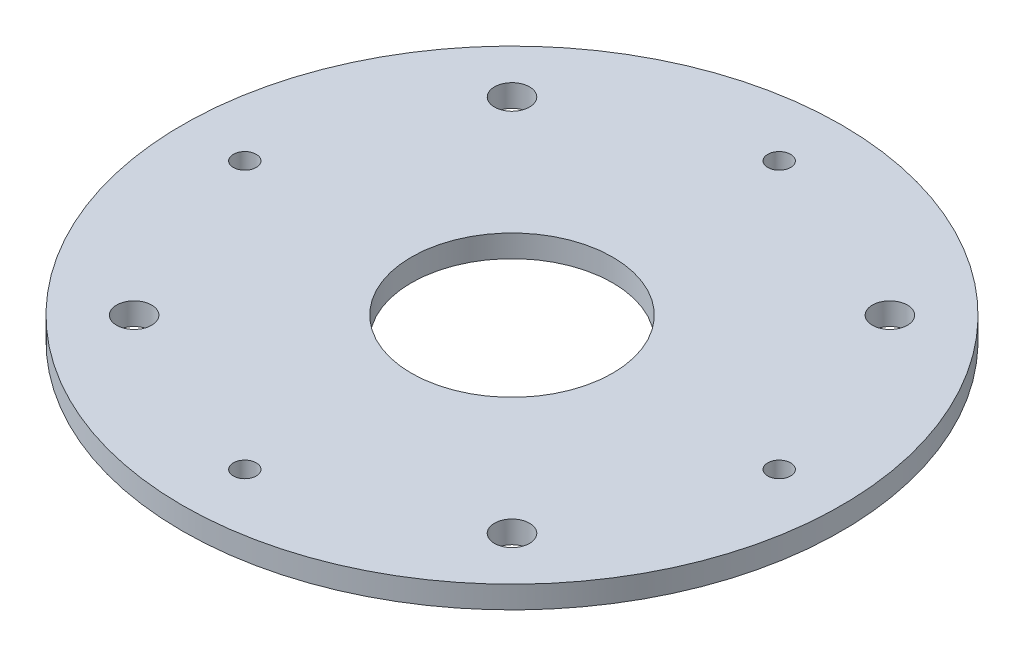
SolidWorks part; units mm, degrees
ref_plane "Front Plane" through (0, 0, 0) normal (0, 0, 1) x (1, 0, 0)
ref_plane "Top Plane" through (0, 0, 0) normal (0, 1, 0) x (1, 0, 0)
ref_plane "Right Plane" through (0, 0, 0) normal (1, 0, 0) x (0, 0, -1)
sketch "Sketch1" plane through (0, 0, 0) normal (0, 1, 0) x (1, 0, 0)
  circle A0 centre (0, 0) radius 46.99
  dimension "D1" = 93.98
extrude "Boss-Extrude1" add sketch "Sketch1" along normal blind 3.175
sketch "Sketch2" plane through (0, 3.175, 0) normal (0, 1, 0) x (1, 0, 0)
  circle A0 centre (0, 0) radius 14.351
  dimension "D1" = 28.702
extrude "Cut-Extrude1" cut sketch "Sketch2" against normal blind 3.175
hole_wizard "#4 Clearance Hole1" positions "Sketch4" profile "Sketch3" hole size "#4" standard "ANSI Inch"
sketch "Sketch4" plane through (0, 3.175, 0) normal (0, 1, 0) x (1, 0, 0)
  point P0 (0, 38.1)
  dimension "D1" = 38.1
sketch "Sketch3" plane through (0, 3.175, -38.1) normal (1, 0, 0) x (0, 0, 1)
  line L0 (0, 0) -> (0, 11.1406)
  line L1 (0, 11.1406) -> (1.6319, 10.16)
  line L2 (1.6319, 10.16) -> (1.6319, 0)
  line L5 (1.6319, 0) -> (0, 0)
  line L10 (0, 11.1406) -> (-1.632, 10.16) construction
  line L11 (0, -6.35) -> (0, 107.95) construction
  dimension "Hole Dia." = 3.2639
  dimension "Hole Depth" = 10.16
  dimension "Drill Angle" = 118
pattern_circular "CirPattern1" count 4 every 90 about axis through (0, 3.175, 0) along (0, 1, 0) of "#4 Clearance Hole1"
sketch "Sketch5" plane through (0, 3.175, 0) normal (0, 1, 0) x (1, 0, 0)
  line L0 (0, 0) -> (-26.9408, 26.9408)
  line L1 (0, 38.1) -> (0, -38.1) construction
  circle A0 centre (-26.9408, 26.9408) radius 2.5
  dimension "D1" = 5
  dimension "D2" = 38.1
  dimension "D3" = 45
extrude "Cut-Extrude2" cut sketch "Sketch5" against normal blind 5.08 contours A0 region at (-24.6964, 3.175, -26.0111)
pattern_circular "CirPattern2" count 4 every 90 about axis through (0, 3.175, 0) along (0, 1, 0) of "Cut-Extrude2"
